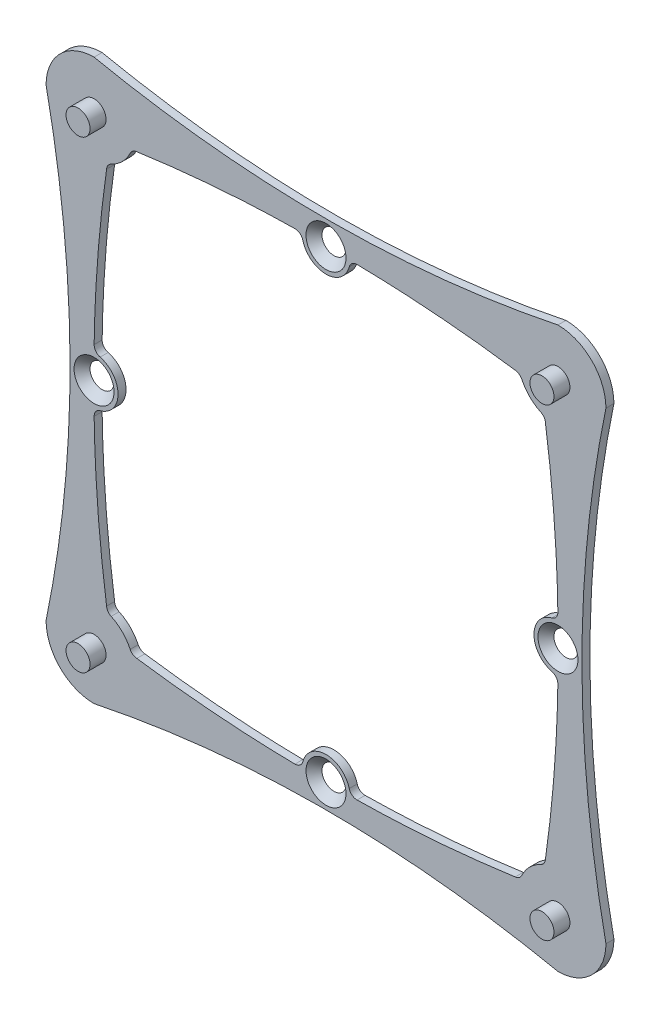
SolidWorks part; units mm, degrees
ref_plane "Ön Düzlem" through (0, 0, 0) normal (0, 0, 1) x (1, 0, 0)
ref_plane "Üst Düzlem" through (0, 0, 0) normal (0, 1, 0) x (1, 0, 0)
ref_plane "Sağ Düzlem" through (0, 0, 0) normal (1, 0, 0) x (0, 0, -1)
sketch "Çizim3" plane through (0, 0, 0) normal (0, 0, 1) x (1, 0, 0)
  line L0 (0, 0) -> (0, 16.417) construction
  line L1 (15.3552, 0) -> (-13.0682, 0) construction
  arc A0 (-29, 35) -> (-35, 29) centre (-29, 29) ccw
  arc A1 (29, 35) -> (35, 29) centre (29, 29) cw
  arc A2 (29, -35) -> (35, -29) centre (29, -29) ccw
  arc A3 (-29, -35) -> (-35, -29) centre (-29, -29) cw
  circle A4 centre (29, 29) radius 1.5
  circle A5 centre (-29, -29) radius 1.5
  circle A6 centre (29, -29) radius 1.5
  circle A7 centre (0, 29) radius 1.5
  circle A8 centre (29, 0) radius 1.5
  arc A9 (-24.48, -26.8624) -> (-26.8624, -24.48) centre (-29, -29) ccw
  circle A10 centre (0, -29) radius 1.5
  arc A11 (-24.48, -26.8624) -> (-23.6565, -27.4317) centre (-23.5759, -26.4349) ccw
  arc A12 (-27.4317, -23.6565) -> (-26.8624, -24.48) centre (-26.4349, -23.5759) ccw
  circle A13 centre (-29, 0) radius 1.5
  arc A14 (2.9026, -28.2418) -> (-2.9026, -28.2418) centre (0, -29) ccw
  arc A15 (-28.2418, -2.9026) -> (-28.2418, 2.9026) centre (-29, 0) ccw
  arc A16 (-23.6565, 27.4317) -> (-24.48, 26.8624) centre (-23.5759, 26.4349) ccw
  circle A17 centre (-29, 0) radius 1.5
  circle A18 centre (-29, 29) radius 1.5
  circle A19 centre (29, 29) radius 1.5
  circle A20 centre (-29, -29) radius 1.5
  circle A21 centre (29, -29) radius 1.5
  arc A22 (-2.9026, 28.2418) -> (2.9026, 28.2418) centre (0, 29) ccw
  circle A23 centre (0, 29) radius 1.5
  arc A24 (-26.8624, 24.48) -> (-24.48, 26.8624) centre (-29, 29) ccw
  arc A25 (-26.8624, 24.48) -> (-27.4317, 23.6565) centre (-26.4349, 23.5759) ccw
  arc A26 (28.2418, 2.9026) -> (28.2418, -2.9026) centre (29, 0) ccw
  arc A27 (27.4317, 23.6565) -> (26.8624, 24.48) centre (26.4349, 23.5759) ccw
  circle A28 centre (29, 0) radius 1.5
  arc A29 (-3.8854, -28.989) -> (-2.9026, -28.2418) centre (-3.8702, -27.9891) ccw
  arc A30 (3.8854, -28.989) -> (2.9026, -28.2418) centre (3.8702, -27.9891) cw
  arc A31 (24.48, 26.8624) -> (26.8624, 24.48) centre (29, 29) ccw
  arc A32 (24.48, 26.8624) -> (23.6565, 27.4317) centre (23.5759, 26.4349) ccw
  arc A33 (-3.8854, 28.989) -> (-2.9026, 28.2418) centre (-3.8702, 27.9891) cw
  arc A34 (23.6565, -27.4317) -> (24.48, -26.8624) centre (23.5759, -26.4349) ccw
  arc A35 (-28.989, 3.8854) -> (-28.2418, 2.9026) centre (-27.9891, 3.8702) ccw
  arc A36 (-28.989, -3.8854) -> (-28.2418, -2.9026) centre (-27.9891, -3.8702) cw
  arc A37 (28.989, -3.8854) -> (28.2418, -2.9026) centre (27.9891, -3.8702) ccw
  arc A38 (26.8624, -24.48) -> (24.48, -26.8624) centre (29, -29) ccw
  arc A39 (26.8624, -24.48) -> (27.4317, -23.6565) centre (26.4349, -23.5759) ccw
  arc A40 (28.989, 3.8854) -> (28.2418, 2.9026) centre (27.9891, 3.8702) cw
  arc A41 (3.8854, 28.989) -> (2.9026, 28.2418) centre (3.8702, 27.9891) ccw
  spline S0 degree 3 poles (23.6565, -27.4317) (17.082, -28.3692) (10.4916, -28.8883) (3.8854, -28.989) knots 0 0 0 0 0.836152 0.836152 0.836152 0.836152
  spline S1 degree 2 poles (29, -35) (0, -29) (-29, -35) knots 0 0 0 1 1 1
  spline S2 degree 3 poles (-23.6565, -27.4317) (-17.082, -28.3692) (-10.4916, -28.8883) (-3.8854, -28.989) knots 0 0 0 0 0.836152 0.836152 0.836152 0.836152
  spline S3 degree 2 poles (-35, -29) (-29, 0) (-35, 29) knots 0 0 0 1 1 1
  spline S4 degree 3 poles (-27.4317, 23.6565) (-28.3692, 17.082) (-28.8883, 10.4916) (-28.989, 3.8854) knots 0 0 0 0 0.836152 0.836152 0.836152 0.836152
  spline S5 degree 3 poles (-27.4317, -23.6565) (-28.3692, -17.082) (-28.8883, -10.4916) (-28.989, -3.8854) knots 0 0 0 0 0.836152 0.836152 0.836152 0.836152
  spline S6 degree 2 poles (-29, 35) (0, 29) (29, 35) knots 0 0 0 1 1 1
  spline S7 degree 3 poles (23.6565, 27.4317) (17.082, 28.3692) (10.4916, 28.8883) (3.8854, 28.989) knots 0 0 0 0 0.836152 0.836152 0.836152 0.836152
  spline S8 degree 3 poles (-23.6565, 27.4317) (-17.082, 28.3692) (-10.4916, 28.8883) (-3.8854, 28.989) knots 0 0 0 0 0.836152 0.836152 0.836152 0.836152
  spline S9 degree 2 poles (35, 29) (29, 0) (35, -29) knots 0 0 0 1 1 1
  spline S10 degree 3 poles (27.4317, -23.6565) (28.3692, -17.082) (28.8883, -10.4916) (28.989, -3.8854) knots 0 0 0 0 0.836152 0.836152 0.836152 0.836152
  spline S11 degree 3 poles (27.4317, 23.6565) (28.3692, 17.082) (28.8883, 10.4916) (28.989, 3.8854) knots 0 0 0 0 0.836152 0.836152 0.836152 0.836152
  point P36 (0, 0)
  point P92 (0, 0)
  dimension "D1" = 3
  dimension "D2" = 3
  dimension "D3" = 4
  dimension "D4" = 6
  dimension "D5" = 4
  dimension "D6" = 1
  dimension "D7" = 1
  dimension "D8" = 1
  dimension "D9" = 1
extrude "Yükseklik-Ekstrüzyon3" add sketch "Çizim3" along normal blind 1 contours S9 A1 S6 A0 S3 A3 S1 A2 A39 A38 A34 A29 S2 A11 A9 A12 A25 A24 A16 A35 A32 A31 A27 region at (0, 31.0101, 0)
sketch "Çizim4" plane through (0, 0, 1) normal (0, 0, 1) x (1, 0, 0)
  circle A0 centre (-29, 29) radius 1.5
  circle A1 centre (29, 29) radius 1.5
  circle A2 centre (29, -29) radius 1.5
  circle A3 centre (-29, -29) radius 1.5
  point P12 (0, 0)
  dimension "D1" = 4
chamfer "Pah1" distance 1 angle 45 4 edges at (1.5, 29, 1) (1.5, -29, 1) (30.5, 0, 1) (-27.5, 0, 1)
sketch "Çizim5" plane through (0, 0, 1) normal (0, 0, 1) x (1, 0, 0)
  circle A0 centre (-29, 29) radius 1.5
  circle A1 centre (29, 29) radius 1.5
  circle A2 centre (29, -29) radius 1.5
  circle A3 centre (-29, -29) radius 1.5
  point P12 (0, 0)
  dimension "D1" = 4
extrude "Yükseklik-Ekstrüzyon5" add sketch "Çizim5" along normal blind 2 and the other way blind 1
extrude "Yükseklik-Ekstrüzyon4" add sketch "Çizim4" along normal blind 2 and the other way blind 1
